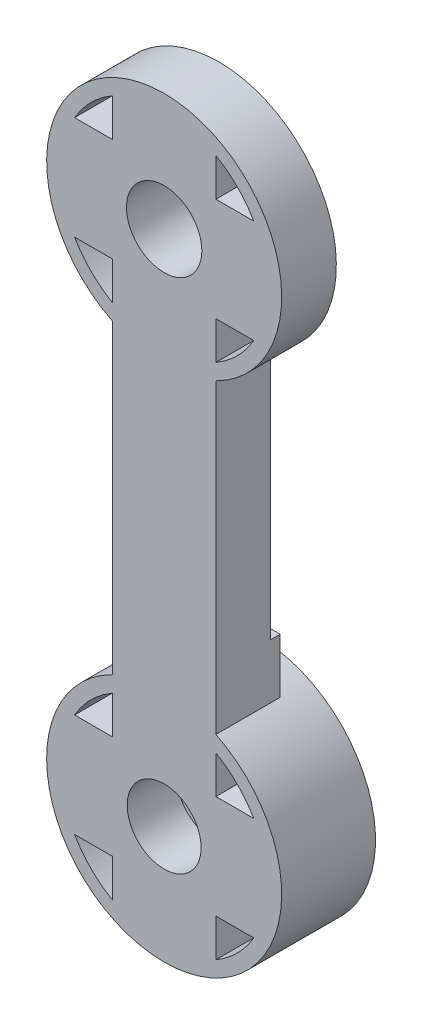
SolidWorks part; units mm, degrees
ref_plane "Front Plane" through (0, 0, 0) normal (0, 0, 1) x (1, 0, 0)
ref_plane "Top Plane" through (0, 0, 0) normal (0, 1, 0) x (1, 0, 0)
ref_plane "Right Plane" through (0, 0, 0) normal (1, 0, 0) x (0, 0, -1)
sketch "Sketch1" plane through (0, 0, 0) normal (0, 0, 1) x (1, 0, 0)
  line L5 (0, -17.5) -> (12.7696, -17.5) construction
  line L26 (0, 0) -> (0, -35) construction
  line L32 (0, 3.5) -> (7.1381, 3.5)
  line L33 (7.1381, 3.5) -> (-7.1381, 3.5)
  line L34 (0, -3.5) -> (7.1381, -3.5)
  line L35 (7.1381, -3.5) -> (-7.1381, -3.5)
  line L36 (3.5, -35) -> (3.5, -41.0622)
  line L37 (-3.5, -35) -> (-3.5, -41.0622)
  line L38 (-3.5, 0) -> (-3.5, 6.0622)
  line L45 (-3.5, 0) -> (-3.5, -35)
  line L47 (3.5, 0) -> (3.5, -35)
  line L48 (3.5, 0) -> (3.5, 6.0622)
  line L49 (7.1381, -31.5) -> (-7.1381, -31.5)
  line L50 (0, -31.5) -> (7.1381, -31.5)
  line L51 (7.1381, -38.5) -> (-7.1381, -38.5)
  line L52 (0, -38.5) -> (7.1381, -38.5)
  circle A0 centre (0, 0) radius 7.95
  circle A1 centre (0, 0) radius 3.5
  circle A2 centre (0, 0) radius 7
  circle A6 centre (0, 0) radius 1.5
  circle A11 centre (0, -35) radius 1.5
  circle A12 centre (0, -35) radius 7
  circle A13 centre (0, -35) radius 3.5
  circle A14 centre (0, -35) radius 7.95
  point P20 (0, -35)
  point P34 (0, -35)
  point P42 (0, 0)
  dimension "D1" = 15.9
  dimension "D2" = 7
  dimension "D6" = 14
  dimension "D9" = 3
  dimension "D3" = 7
  dimension "D7" = 35
extrude "Boss-Extrude4" add sketch "Sketch1" along normal blind 3 contours L48 A2 L38 L33 L32 | A2 L32 A0 L33 | L45 A14 L47 A0 | A14 L51 A12 | A12 L36 L51 L37 | A14 L49 A12 L51 | L36 A13 L51 | L51 A13 L37 | A14 L51 A12 L49 | A13 A11 | L45 A13 L49 | L49 A13 L47 | A12 L45 L49 L47 | A14 L49 A12 L45 | A14 L47 A12 L49 | A14 L45 A12 L47 | A12 L51 L37 L45 L49 | A12 L50 L47 L36 L52 | L45 A2 L47 L34 L35 | A2 L45 A0 L47 | A2 L47 A0 L34 | A2 L34 A0 L32 | A2 L33 A0 L35 | A2 L35 A0 L45 | L33 A2 L35 L45 L38 | L35 A2 L33 L48 L47 | A1 L34 L47 | A1 A6 | A1 L45 L35 | A1 L33 L38 | A1 L48 L32 region at (0, 5.1101, 0) region at (-2.7182, 2.7182, 0) region at (2.7182, 2.7182, 0) region at (2.4049, 2.4049, 0) region at (5.1101, 0, 0) region at (-5.1101, 0, 0) region at (2.7182, -2.7182, 0) region at (-2.7182, -2.7182, 0) region at (5.0555, 5.0555, 0) region at (7.1812, 0, 0) region at (-7.1812, 0, 0) region at (0, -5.1101, 0) region at (-5.2259, -5.2259, 0) region at (5.2259, -5.2259, 0) region at (0, -7.1812, 0) region at (0, -17.5, 0) region at (5.2259, -29.7741, 0) region at (0, -27.8188, 0) region at (-5.2259, -29.7741, 0) region at (0, -29.8899, 0) region at (7.1812, -35, 0) region at (-7.1812, -35, 0) region at (5.1101, -35, 0) region at (2.7182, -32.2818, 0) region at (-2.7182, -32.2818, 0) region at (-5.1101, -35, 0) region at (-6.6001, -38.6495, 0) region at (2.4049, -37.4049, 0) region at (2.7182, -37.7182, 0) region at (-2.7182, -37.7182, 0) region at (0, -40.1101, 0)
sketch "Sketch3" plane through (0, 0, 0) normal (0, 0, -1) x (-1, 0, 0)
  line L0 (-3.5, 6.0622) -> (-3.5, 3.5)
  line L1 (-3.5, 3.5) -> (-6.0622, 3.5)
  line L2 (-3.5, -6.0622) -> (-3.5, -3.5)
  line L3 (-3.5, -3.5) -> (-6.0622, -3.5)
  line L4 (3.5, -6.0622) -> (3.5, -3.5)
  line L5 (3.5, -3.5) -> (6.0622, -3.5)
  line L6 (3.5, 6.0622) -> (3.5, 3.5)
  line L7 (3.5, 3.5) -> (6.0622, 3.5)
  line L8 (0, 0) -> (0, -35) construction
  line L9 (0, -35) -> (0, -17.5) construction
  line L10 (0, -17.5) -> (14.5774, -17.5) construction
  line L11 (-3.5, 3.5) -> (-6.0622, 3.5)
  line L12 (-3.5, 6.0622) -> (-3.5, 3.5)
  line L13 (-3.5, -3.5) -> (-6.0622, -3.5)
  line L14 (-3.5, -6.0622) -> (-3.5, -3.5)
  line L15 (3.5, -3.5) -> (6.0622, -3.5)
  line L16 (3.5, -6.0622) -> (3.5, -3.5)
  line L17 (3.5, 3.5) -> (6.0622, 3.5)
  line L18 (3.5, 6.0622) -> (3.5, 3.5)
  line L19 (3.5, -41.0622) -> (3.5, -38.5)
  line L20 (3.5, -38.5) -> (6.0622, -38.5)
  line L21 (3.5, -28.9378) -> (3.5, -31.5)
  line L22 (3.5, -31.5) -> (6.0622, -31.5)
  line L23 (-3.5, -28.9378) -> (-3.5, -31.5)
  line L24 (-3.5, -31.5) -> (-6.0622, -31.5)
  line L25 (-3.5, -41.0622) -> (-3.5, -38.5)
  line L26 (-3.5, -38.5) -> (-6.0622, -38.5)
  line L27 (3.5, -38.5) -> (6.0622, -38.5)
  line L28 (3.5, -41.0622) -> (3.5, -38.5)
  line L29 (3.5, -31.5) -> (6.0622, -31.5)
  line L30 (3.5, -28.9378) -> (3.5, -31.5)
  line L31 (-3.5, -31.5) -> (-6.0622, -31.5)
  line L32 (-3.5, -28.9378) -> (-3.5, -31.5)
  line L33 (-3.5, -38.5) -> (-6.0622, -38.5)
  line L34 (-3.5, -41.0622) -> (-3.5, -38.5)
  circle A0 centre (0, 0) radius 1.5
  circle A1 centre (0, 0) radius 7.95
  circle A2 centre (0, 0) radius 7
  circle A3 centre (0, -35) radius 7
  circle A4 centre (0, -35) radius 7.95
  circle A5 centre (0, -35) radius 1.5
  line M2 (3.5, -38.5) -> (6.0622, -38.5)
  arc M3 (6.0622, -38.5) -> (3.5, -41.0622) centre (0, -35) cw
  line M4 (3.5, -41.0622) -> (3.5, -38.5)
  line M5 (-3.5, -38.5) -> (-3.5, -41.0622)
  arc M6 (-3.5, -41.0622) -> (-6.0622, -38.5) centre (0, -35) cw
  line M7 (-6.0622, -38.5) -> (-3.5, -38.5)
  arc M9 (3.5, -7.1381) -> (-3.5, -7.1381) centre (0, 0) ccw
  arc M11 (-3.5, -27.8619) -> (3.5, -27.8619) centre (0, -35) ccw
  line M12 (6.0622, -31.5) -> (3.5, -31.5)
  line M13 (3.5, -31.5) -> (3.5, -28.9378)
  arc M14 (3.5, -28.9378) -> (6.0622, -31.5) centre (0, -35) cw
  arc M15 (-3.5, -6.0622) -> (-6.0622, -3.5) centre (0, 0) cw
  line M16 (-6.0622, -3.5) -> (-3.5, -3.5)
  line M17 (-3.5, -3.5) -> (-3.5, -6.0622)
  line M18 (-3.5, -31.5) -> (-6.0622, -31.5)
  arc M19 (-6.0622, -31.5) -> (-3.5, -28.9378) centre (0, -35) cw
  line M20 (-3.5, -28.9378) -> (-3.5, -31.5)
  line M21 (3.5, -3.5) -> (6.0622, -3.5)
  arc M22 (6.0622, -3.5) -> (3.5, -6.0622) centre (0, 0) cw
  line M23 (3.5, -6.0622) -> (3.5, -3.5)
  line M24 (6.0622, 3.5) -> (3.5, 3.5)
  line M25 (3.5, 3.5) -> (3.5, 6.0622)
  arc M26 (3.5, 6.0622) -> (6.0622, 3.5) centre (0, 0) cw
  arc M27 (-6.0622, 3.5) -> (-3.5, 6.0622) centre (0, 0) cw
  line M28 (-3.5, 6.0622) -> (-3.5, 3.5)
  line M29 (-3.5, 3.5) -> (-6.0622, 3.5)
  circle M30 centre (0, 0) radius 1.5
  circle M31 centre (0, -35) radius 1.5
  dimension "D1" = 15.9
extrude "Boss-Extrude5" add sketch "Sketch3" along normal blind 3 contours A1 A2 M9 M26 M22 M15 M27 | A2 M25 M28 M29 M16 M17 M23 M21 M24 M30 | A3 M4 M2 M12 M13 M20 M18 M7 M5 M31 | A4 A3 M11 M3 M6 M19 M14 region at (0, 6.802, 0) region at (0, -41.802, 0) region at (-6.5556, -4.0868, 0) region at (4.0868, -41.5556, 0)
sketch "Sketch4" plane through (0, 0, 3) normal (0, 0, 1) x (1, 0, 0)
  line L0 (0, 0) -> (0, -35) construction
  line L1 (0, -35) -> (0, 0) construction
  line L2 (0, -17.5) -> (19.6941, -17.5) construction
  circle A1 centre (0, -35) radius 2.5
  circle A2 centre (0, 0) radius 2.5
  dimension "D2" = 5
extrude "Cut-Extrude1" cut sketch "Sketch4" against normal blind 1.5
sketch "Sketch5" plane through (0, 0, -3) normal (0, 0, -1) x (-1, 0, 0)
  circle A0 centre (0, 0) radius 7
extrude "Cut-Extrude2" cut sketch "Sketch5" against normal blind 2
sketch "Sketch6" plane through (0, 0, -3) normal (0, 0, -1) x (-1, 0, 0)
  circle A0 centre (0, -35) radius 7.95
extrude "Cut-Extrude3" cut sketch "Sketch6" against normal blind 1
sketch "Sketch7" plane through (0, 0, 1.5) normal (0, 0, 1) x (1, 0, 0)
  circle A0 centre (0, -35) radius 2.5
extrude "Cut-Extrude4" cut sketch "Sketch7" against normal blind 1.85
sketch "Sketch8" plane through (0, 0, -3) normal (0, 0, -1) x (-1, 0, 0)
  circle A0 centre (0, 0) radius 7.95
  circle A1 centre (0, 0) radius 7
extrude "Boss-Extrude6" add sketch "Sketch8" along normal blind 0.7
sketch "Sketch9" plane through (0, 0, -2) normal (0, 0, -1) x (-1, 0, 0)
  line L0 (-3.5, -28.9378) -> (-3.5, -31.5)
  line L1 (-3.5, -31.5) -> (-6.0622, -31.5)
  line L2 (-6.0622, -38.5) -> (-3.5, -38.5)
  line L3 (-3.5, -38.5) -> (-3.5, -41.0622)
  line L4 (6.0622, -38.5) -> (3.5, -38.5)
  line L5 (3.5, -38.5) -> (3.5, -41.0622)
  line L6 (3.5, -28.9378) -> (3.5, -31.5)
  line L7 (3.5, -31.5) -> (6.0622, -31.5)
  circle A0 centre (0, -35) radius 7.95
  circle A1 centre (0, -35) radius 7
  circle A2 centre (0, -35) radius 1.5
  line M1 (6.0622, -31.5) -> (3.5, -31.5)
  line M2 (3.5, -31.5) -> (3.5, -28.9378)
  arc M3 (3.5, -28.9378) -> (6.0622, -31.5) centre (0, -35) cw
  arc M4 (-3.5, -41.0622) -> (-6.0622, -38.5) centre (0, -35) cw
  line M5 (-6.0622, -38.5) -> (-3.5, -38.5)
  line M6 (-3.5, -38.5) -> (-3.5, -41.0622)
  arc M7 (6.0622, -38.5) -> (3.5, -41.0622) centre (0, -35) cw
  line M8 (3.5, -41.0622) -> (3.5, -38.5)
  line M9 (3.5, -38.5) -> (6.0622, -38.5)
  circle M10 centre (0, -35) radius 7.95
  line M11 (-3.5, -31.5) -> (-6.0622, -31.5)
  arc M12 (-6.0622, -31.5) -> (-3.5, -28.9378) centre (0, -35) cw
  line M13 (-3.5, -28.9378) -> (-3.5, -31.5)
  circle M14 centre (0, -35) radius 1.5
extrude "Boss-Extrude8" add sketch "Sketch9" along normal blind 0.7 contours A1 M2 M13 M11 M5 M6 M8 M9 M1 M14 | A1 M10 M3 M7 M4 M12 region at (0, -28.198, -2) region at (7.7251, -35, -2)
sketch "Sketch10" plane through (0, 0, 0) normal (0, 0, -1) x (-1, 0, 0)
  line L2 (-3.5, -7.1381) -> (-3.5, -27.8619)
  line L4 (3.5, -7.1381) -> (3.5, -27.8619)
  circle A0 centre (0, 0) radius 7.95
  circle A1 centre (0, -35) radius 7.95
  line M1 (-3.5, -7.1381) -> (-3.5, -27.8619)
  arc M2 (-3.5, -27.8619) -> (3.5, -27.8619) centre (0, -35) cw
  line M3 (3.5, -27.8619) -> (3.5, -7.1381)
  arc M4 (3.5, -7.1381) -> (-3.5, -7.1381) centre (0, 0) cw
extrude "Boss-Extrude9" add sketch "Sketch10" along normal blind 0.7 contours M4 M1 M2 M3 region at (0, -17.5, 0)
sketch "Sketch11" plane through (3.5, 0, 0) normal (1, 0, 0) x (0, 0, -1)
  line L0 (-3, -42.95) -> (2.7, -42.95) construction
  line L1 (3.7, 7.95) -> (0.7, 7.95)
  line L2 (3.7, 7.95) -> (3.7, -7.95)
  line L3 (3.7, -7.95) -> (0.7, -7.95)
  line L4 (0.7, 7.95) -> (0.7, -7.95)
  line L5 (2.7, -27.05) -> (0.7, -27.05)
  line L6 (2.7, -27.05) -> (2.7, -42.95)
  line L7 (2.7, -42.95) -> (0.7, -42.95)
  line L8 (0.7, -27.05) -> (0.7, -42.95)
extrude "Cut-Extrude5" cut sketch "Sketch11" against normal through all both and the other way through all
sketch "Sketch12" plane through (0, 0, -0.7) normal (0, 0, -1) x (-1, 0, 0)
  line L0 (3.5, -27.8619) -> (3.5, -7.1381) construction
  line L1 (-3.5, -27.8619) -> (3.5, -27.8619)
  line L2 (-3.5, -27.8619) -> (-3.5, -24.1619)
  line L3 (-3.5, -24.1619) -> (3.5, -24.1619)
  line L4 (3.5, -27.8619) -> (3.5, -24.1619)
  circle A0 centre (0, -35) radius 7.95
  line M3 (3.5, -27.8619) -> (3.5, -7.1381)
  line M5 (-3.5, -7.1381) -> (-3.5, -27.8619)
  dimension "D1" = 3.7
extrude "Boss-Extrude10" add sketch "Sketch12" along normal blind 0.65 contours A0 L3 M3 M5 region at (0, -25.7475, -0.7)
sketch "Sketch13" plane through (0, 0, -0.7) normal (0, 0, -1) x (-1, 0, 0)
  line L0 (-6.0622, -31.5) -> (-3.5, -31.5)
  line L1 (-3.5, -31.5) -> (-3.5, -28.9378)
  line L2 (3.5, -28.9378) -> (3.5, -31.5)
  line L3 (3.5, -31.5) -> (6.0622, -31.5)
  line L4 (-6.0622, -38.5) -> (-3.5, -38.5)
  line L5 (-3.5, -38.5) -> (-3.5, -41.0622)
  line L6 (6.0622, -38.5) -> (3.5, -38.5)
  line L7 (3.5, -38.5) -> (3.5, -41.0622)
  circle A0 centre (0, -35) radius 1.5
  circle A1 centre (0, -35) radius 7.95
  circle A2 centre (0, -35) radius 7
  arc M1 (-6.0622, -31.5) -> (-3.5, -28.9378) centre (0, -35) cw
  line M2 (-3.5, -28.9378) -> (-3.5, -31.5)
  line M3 (-3.5, -31.5) -> (-6.0622, -31.5)
  line M4 (3.5, -31.5) -> (3.5, -28.9378)
  arc M5 (3.5, -28.9378) -> (6.0622, -31.5) centre (0, -35) cw
  line M6 (6.0622, -31.5) -> (3.5, -31.5)
  line M7 (3.5, -38.5) -> (6.0622, -38.5)
  arc M8 (6.0622, -38.5) -> (3.5, -41.0622) centre (0, -35) cw
  line M9 (3.5, -41.0622) -> (3.5, -38.5)
  line M10 (-3.5, -38.5) -> (-3.5, -41.0622)
  arc M11 (-3.5, -41.0622) -> (-6.0622, -38.5) centre (0, -35) cw
  line M12 (-6.0622, -38.5) -> (-3.5, -38.5)
  circle M13 centre (0, -35) radius 1.5
  arc M14 (-3.5, -27.8619) -> (3.5, -27.8619) centre (0, -35) ccw
  arc M15 (3.5, -27.8619) -> (-3.5, -27.8619) centre (0, -35) ccw
extrude "Boss-Extrude11" add sketch "Sketch13" along normal blind 2.65 contours A2 M15 M14 M5 M8 M11 M1 | A2 M4 M2 M3 M12 M10 M9 M7 M6 M13 region at (4.7811, -31.698, -0.7) region at (4.0868, -41.5556, -0.7)
sketch "Sketch14" plane through (0, 0, 3) normal (0, 0, 1) x (1, 0, 0)
  circle A0 centre (0, 0) radius 2.55
  dimension "D1" = 5.1
extrude "Cut-Extrude6" cut sketch "Sketch14" against normal through all
